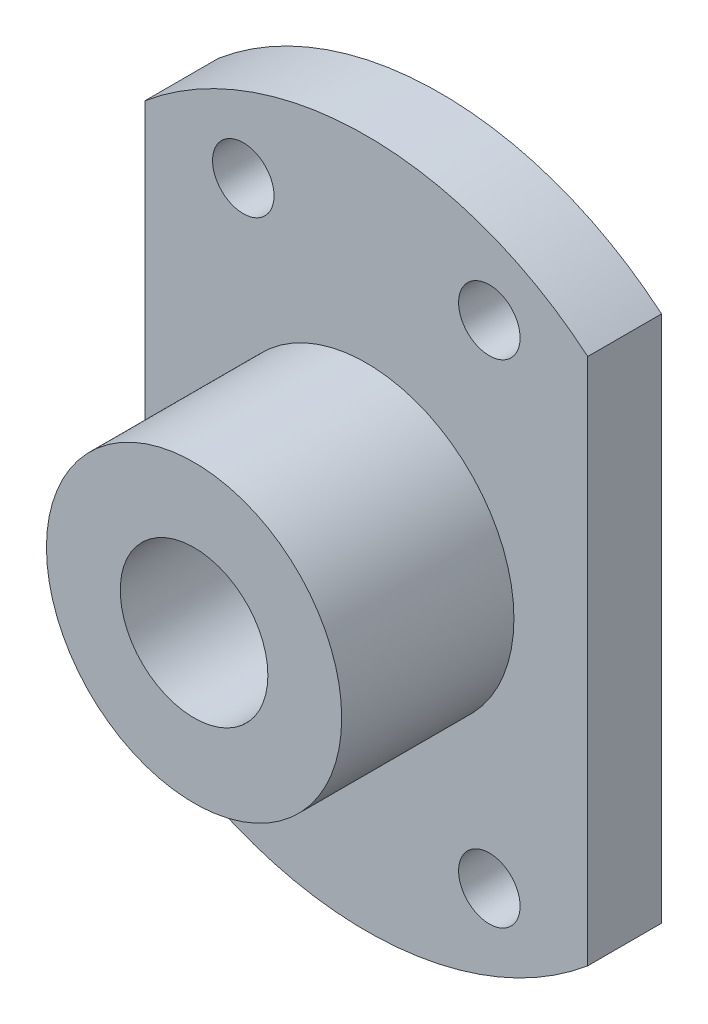
SolidWorks part; units mm, degrees
ref_plane "Front Plane" through (0, 0, 0) normal (0, 0, 1) x (1, 0, 0)
ref_plane "Top Plane" through (0, 0, 0) normal (0, 1, 0) x (1, 0, 0)
ref_plane "Right Plane" through (0, 0, 0) normal (1, 0, 0) x (0, 0, -1)
sketch "Sketch1" plane through (0, 0, 0) normal (0, 0, 1) x (1, 0, 0)
  line L0 (-9, 10.7238) -> (-9, -10.7238)
  line L1 (9, 10.7238) -> (9, -10.7238)
  line L2 (-9, 0) -> (9, 0) construction
  line L3 (-5, 10) -> (5, -10) construction
  line L4 (-5, -10) -> (5, 10) construction
  arc A0 (9, 10.7238) -> (-9, 10.7238) centre (0, 0) ccw
  arc A1 (-9, -10.7238) -> (9, -10.7238) centre (0, 0) ccw
  circle A2 centre (0, 0) radius 3
  circle A3 centre (-5, 10) radius 1.25
  circle A4 centre (5, 10) radius 1.25
  circle A5 centre (-5, -10) radius 1.25
  circle A6 centre (5, -10) radius 1.25
  point P7 (0, 0)
  point P18 (0, 0)
  dimension "D2" = 14
  dimension "D3" = 6
  dimension "D6" = 2.5
  dimension "D1" = 18
  dimension "D4" = 20
  dimension "D5" = 10
extrude "Boss-Extrude1" add sketch "Sketch1" along normal blind 3
sketch "Sketch2" plane through (0, 0, 3) normal (0, 0, 1) x (1, 0, 0)
  circle A0 centre (0, 0) radius 6
  circle A1 centre (0, 0) radius 3
  circle A2 centre (0, 0) radius 3 construction
  dimension "D1" = 12
extrude "LinearBallSupport" add sketch "Sketch2" along normal blind 7
